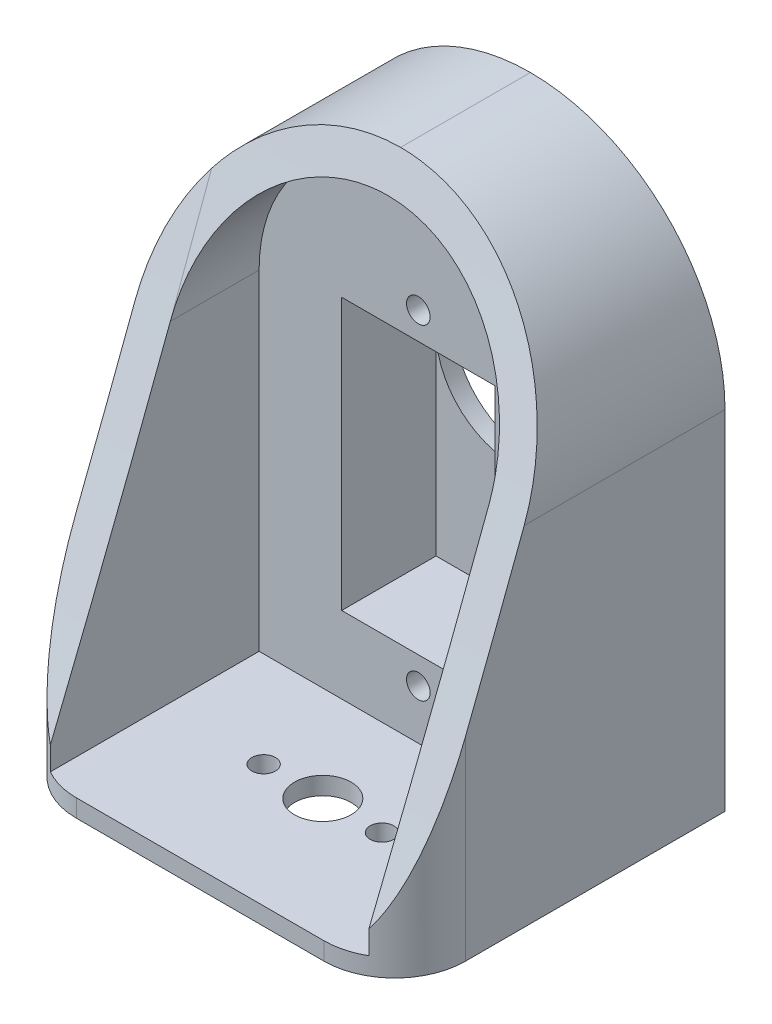
SolidWorks part; units mm, degrees
ref_plane "Front Plane" through (0, 0, 0) normal (0, 0, 1) x (1, 0, 0)
ref_plane "Top Plane" through (0, 0, 0) normal (0, 1, 0) x (1, 0, 0)
ref_plane "Right Plane" through (0, 0, 0) normal (1, 0, 0) x (0, 0, -1)
sketch "Sketch1" plane through (0, 0, 0) normal (0, 1, 0) x (1, 0, 0)
  line L1 (-16.5, -14) -> (16.5, -14)
  line L2 (-16.5, -14) -> (-16.5, 14)
  line L3 (-16.5, 14) -> (16.5, 14)
  line L4 (16.5, -14) -> (16.5, 14)
  line L5 (-16.5, -14) -> (16.5, 14) construction
  line L6 (-16.5, 14) -> (16.5, -14) construction
  point P0 (0, 0)
  dimension "D1" = 33
  dimension "D2" = 28
extrude "Boss-Extrude1" add sketch "Sketch1" along normal blind 46
sketch "Sketch3" plane through (16.5, 0, 0) normal (1, 0, 0) x (0, 0, -1)
  line L2 (-14, 0) -> (14, 0) construction
  line L3 (14, 46) -> (11.5, 46)
  line L4 (14, 46) -> (14, 21)
  line L5 (14, 21) -> (11.5, 21)
  line L6 (11.5, 46) -> (11.5, 21)
  line L7 (-14, 46) -> (4.5, 46)
  line L8 (-14, 46) -> (-14, 1.5)
  line L9 (-14, 1.5) -> (4.5, 1.5)
  line L10 (4.5, 46) -> (4.5, 1.5)
  line M11 (14, 46) -> (-14, 46)
  line M12 (-14, 46) -> (-14, 0)
  dimension "D1" = 1.5
  dimension "D2" = 7
  dimension "D3" = 2.5
  dimension "D4" = 25
extrude "Cut-Extrude2" cut sketch "Sketch3" against normal through all contours L10 L9 M11 M12 region at (16.5, 23.75, 4.75)
sketch "Sketch5" plane through (16.5, 0, 0) normal (1, 0, 0) x (0, 0, -1)
  line L0 (4.5, 46) -> (3, 46)
  line L1 (4.5, 46) -> (4.5, 1.5)
  line L2 (4.5, 1.5) -> (-14, 1.5)
  spline S0 degree 2 poles (3, 46) (-4.9798, 23.5484) (-14, 1.5) knots 0 0 0 1 1 1
  dimension "D1" = 1.5
extrude "Boss-Extrude2" add sketch "Sketch5" against normal blind 3
sketch "Sketch6" plane through (-16.5, 0, 0) normal (-1, 0, 0) x (0, 0, 1)
  line L3 (-3, 46) -> (-4.5, 46)
  line L4 (-4.5, 46) -> (-4.5, 1.5)
  line L5 (-4.5, 1.5) -> (14, 1.5)
  line L6 (-3, 46) -> (-4.5, 46)
  line L7 (-4.5, 46) -> (-4.5, 1.5)
  line L8 (-4.5, 1.5) -> (14, 1.5)
  parabola Q1 (14, 1.5) -> (-3, 46) focus (481.0865, 202.8081) apex (7.0012, 19.0718)
  parabola Q2 (14, 1.5) -> (-3, 46) focus (481.0865, 202.8081) apex (7.0012, 19.0718)
  dimension "D1" = 0
extrude "Boss-Extrude3" add sketch "Sketch6" against normal blind 3
sketch "Sketch8" plane through (13.5, 0, 0) normal (-1, 0, 0) x (0, 0, 1)
  line L0 (-4.5, 43) -> (-1.9284, 43)
  line L1 (-4.5, 1.5) -> (-4.5, 46) construction
  line L2 (-4.5, 46) -> (-3, 46) construction
  line L6 (-3, 46) -> (-4.5, 46)
  line L7 (-4.5, 46) -> (-4.5, 1.5)
  line L8 (-4.5, 1.5) -> (14, 1.5)
  line L9 (-3, 46) -> (-4.5, 46)
  line L10 (-4.5, 46) -> (-4.5, 1.5)
  line L11 (-4.5, 1.5) -> (14, 1.5)
  parabola Q0 (-3, 46) -> (14, 1.5) focus (481.0865, 202.8081) apex (7.0012, 19.0718) construction
  parabola Q2 (14, 1.5) -> (-3, 46) focus (481.0865, 202.8081) apex (7.0012, 19.0718)
  parabola Q3 (14, 1.5) -> (-3, 46) focus (481.0865, 202.8081) apex (7.0012, 19.0718)
  spline M2 degree 2 poles (-3, 46) (4.9798, 23.5484) (14, 1.5) knots 0 0 0 1 1 1
  line M3 (-3, 46) -> (-4.5, 46)
  line M4 (-4.5, 46) -> (-4.5, 1.5)
  dimension "D1" = 3
  dimension "D2" = 0
extrude "Boss-Extrude4" add sketch "Sketch8" along normal up to surface (27 mm away) contours L0 M4 M2 M3 region at (13.5, 44.3684, -3.459) up to face at (-13.5, 18.1875, 0.3125)
fillet "Fillet2" radius 13.5 2 edges
fillet "Fillet3" radius 16.5 2 edges at (-16.5, 46, -8.5) (16.5, 46, -8.5)
sketch "Sketch9" plane through (0, 0, -4.5) normal (0, 0, 1) x (1, 0, 0)
  line L0 (-13.5, 1.5) -> (13.5, 1.5) construction
  line L1 (-6.5, 8) -> (6.5, 8)
  line L2 (-6.5, 8) -> (-6.5, 31)
  line L3 (-6.5, 31) -> (6.5, 31)
  line L4 (6.5, 8) -> (6.5, 31)
  line L5 (-6.5, 8) -> (6.5, 31) construction
  line L6 (-6.5, 31) -> (6.5, 8) construction
  point P0 (0, 19.5)
  dimension "D1" = 13
  dimension "D2" = 23
  dimension "D3" = 6.5
sketch "Sketch18" plane through (0, 1.5, 0) normal (0, 1, 0) x (1, 0, 0)
  line L0 (0, 3) -> (0, 14) construction
  circle A0 centre (0, -3.5999) radius 2.4
  circle A1 centre (5.0159, -3.5999) radius 1
  circle A2 centre (-5.0159, -3.5999) radius 1
extrude "Cut-Extrude10" cut sketch "Sketch18" against normal through all
extrude "Cut-Extrude4" cut sketch "Sketch9" against normal blind 8
sketch "Sketch10" plane through (0, 0, -12.5) normal (0, 0, 1) x (1, 0, 0)
  line L1 (6.5, 31) -> (-6.5, 31) construction
  circle A0 centre (0, 24.5) radius 6.5
  dimension "D1" = 13
  dimension "D2" = 6.5
extrude "Cut-Extrude5" cut sketch "Sketch10" against normal through all
sketch "Sketch11" plane through (0, 0, -4.5) normal (0, 0, 1) x (1, 0, 0)
  line L1 (6.5, 31) -> (0, 31) construction
  circle A0 centre (0, 33.3) radius 1
  circle A1 centre (0, 5.7) radius 1
  dimension "D1" = 27.6
  dimension "D2" = 2
  dimension "D3" = 2
  dimension "D4" = 2.3
extrude "Cut-Extrude6" cut sketch "Sketch11" against normal blind 8
fillet "Fillet4" radius 6 2 edges at (-16.5, 0.75, 14) (16.5, 0.75, 14)
